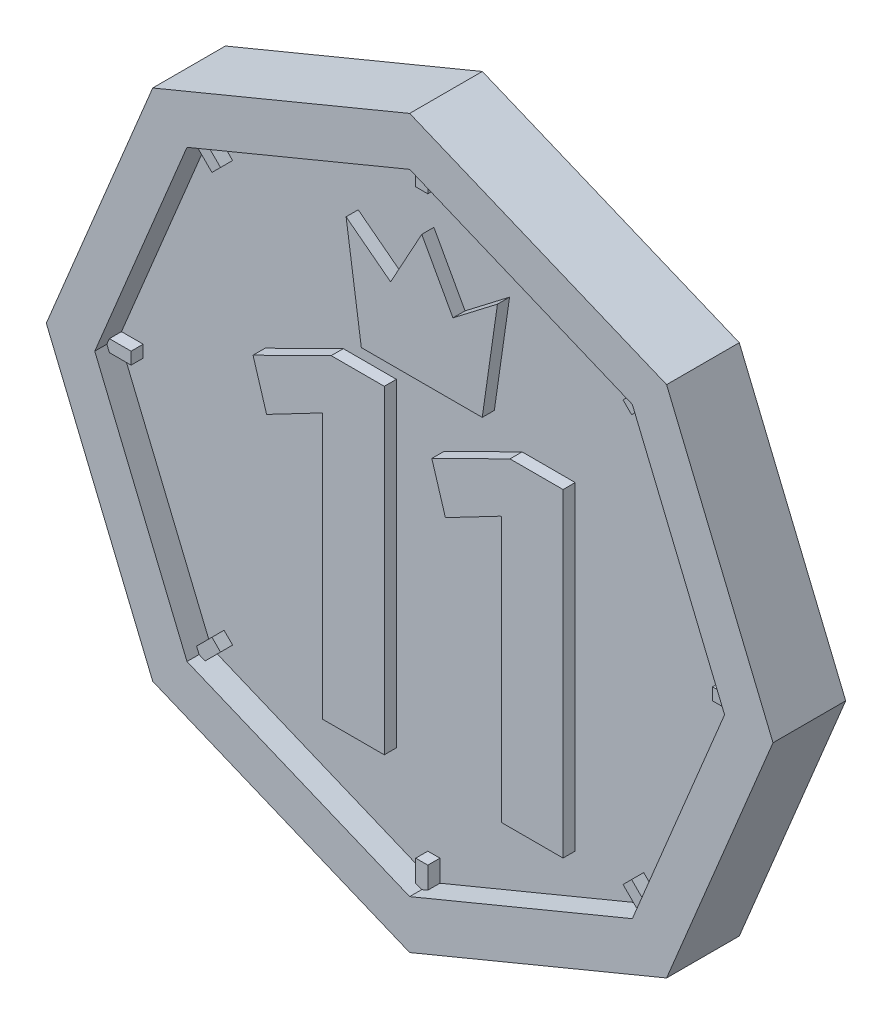
SolidWorks part; units mm, degrees
ref_plane "Front Plane" through (0, 0, 0) normal (0, 0, 1) x (1, 0, 0)
ref_plane "Top Plane" through (0, 0, 0) normal (0, 1, 0) x (1, 0, 0)
ref_plane "Right Plane" through (0, 0, 0) normal (1, 0, 0) x (0, 0, -1)
sketch "Sketch1" plane through (0, 0, 0) normal (0, 0, 1) x (1, 0, 0)
  line L0 (-26.9408, -26.9408) -> (0, -38.1)
  line L1 (38.1, 0) -> (26.9408, 26.9408)
  line L2 (26.9408, 26.9408) -> (0, 38.1)
  line L3 (0, 38.1) -> (-26.9408, 26.9408)
  line L4 (-26.9408, 26.9408) -> (-38.1, 0)
  line L5 (-38.1, 0) -> (-26.9408, -26.9408)
  line L6 (0, -38.1) -> (26.9408, -26.9408)
  line L7 (26.9408, -26.9408) -> (38.1, 0)
  line L8 (38.1, 0) -> (-38.1, 0) construction
  line L19 (33.02, 0) -> (23.3487, 23.3487)
  line L20 (23.3487, 23.3487) -> (0, 33.02)
  line L21 (0, 33.02) -> (-23.3487, 23.3487)
  line L22 (-23.3487, 23.3487) -> (-33.02, 0)
  line L23 (-33.02, 0) -> (-23.3487, -23.3487)
  line L24 (-23.3487, -23.3487) -> (0, -33.02)
  line L25 (0, -33.02) -> (23.3487, -23.3487)
  line L26 (23.3487, -23.3487) -> (33.02, 0)
  circle A0 centre (0, 0) radius 35.1998 construction
  circle A1 centre (0, 0) radius 30.5065 construction
  dimension "D1" = 76.2
  dimension "D4" = 5.08
extrude "Boss-Extrude2" add sketch "Sketch1" along normal blind 2.54 contours L25 L26 L19 L20 L21 L22 L23 L24 | L19 L20 L21 L22 L23 L24 L25 L26 region at (0, 0, 0)
extrude "Boss-Extrude3" add sketch "Sketch1<3>" along normal blind 5.08 and the other way blind 2.54 contours L6 L7 L1 L2 L3 L4 L5 L0 L26 L25 L24 L23 L22 L21 L20 L19 region at (-31.5248, -13.058, 0)
sketch "Sketch1<3>" plane through (0, 0, 0) normal (0, 0, 1) x (1, 0, 0) same geometry as "Sketch1"
sketch "Sketch2" plane through (0, 0, 2.54) normal (0, 0, 1) x (1, 0, 0)
  line L0 (-21.5859, -23.0332) -> (18.1114, -23.0332) construction
  line L2 (0, 33.02) -> (0, -33.02) construction
  line L3 (-6.3393, 13.0307) -> (6.3393, 13.0307)
  line L4 (6.3393, 13.0307) -> (7.935, 24.113)
  line L5 (7.935, 24.113) -> (3.2684, 20.5338)
  line L6 (3.2684, 20.5338) -> (0, 26.4848)
  line L7 (-3.2684, 20.5338) -> (0, 26.4848)
  line L8 (-7.935, 24.113) -> (-3.2684, 20.5338)
  line L9 (-6.3393, 13.0307) -> (-7.935, 24.113)
  line L20 (-23.7977, -22.8997) -> (-22.0016, -21.1036)
  line L21 (-0.635, -33.02) -> (0.635, -33.02)
  line L22 (-0.635, -33.02) -> (-0.635, -30.48)
  line L23 (-0.635, -30.48) -> (0.635, -30.48)
  line L24 (0.635, -33.02) -> (0.635, -30.48)
  line L25 (-0.635, -33.02) -> (0.635, -30.48) construction
  line L26 (-0.635, -30.48) -> (0.635, -33.02) construction
  line L27 (-23.7977, -22.8997) -> (-22.8997, -23.7977)
  line L28 (-22.8997, -23.7977) -> (-21.1036, -22.0016)
  line L29 (-22.0016, -21.1036) -> (-21.1036, -22.0016)
  line L30 (-33.02, 0.635) -> (-30.48, 0.635)
  line L31 (-33.02, 0.635) -> (-33.02, -0.635)
  line L32 (-33.02, -0.635) -> (-30.48, -0.635)
  line L33 (-30.48, 0.635) -> (-30.48, -0.635)
  line L34 (-22.8997, 23.7977) -> (-21.1036, 22.0016)
  line L35 (-22.8997, 23.7977) -> (-23.7977, 22.8997)
  line L36 (-23.7977, 22.8997) -> (-22.0016, 21.1036)
  line L37 (-21.1036, 22.0016) -> (-22.0016, 21.1036)
  line L38 (0.635, 33.02) -> (0.635, 30.48)
  line L39 (0.635, 33.02) -> (-0.635, 33.02)
  line L40 (-0.635, 33.02) -> (-0.635, 30.48)
  line L41 (0.635, 30.48) -> (-0.635, 30.48)
  line L42 (23.7977, 22.8997) -> (22.0016, 21.1036)
  line L43 (23.7977, 22.8997) -> (22.8997, 23.7977)
  line L44 (22.8997, 23.7977) -> (21.1036, 22.0016)
  line L45 (22.0016, 21.1036) -> (21.1036, 22.0016)
  line L46 (33.02, -0.635) -> (30.48, -0.635)
  line L47 (33.02, -0.635) -> (33.02, 0.635)
  line L48 (33.02, 0.635) -> (30.48, 0.635)
  line L49 (30.48, -0.635) -> (30.48, 0.635)
  line L50 (22.8997, -23.7977) -> (21.1036, -22.0016)
  line L51 (22.8997, -23.7977) -> (23.7977, -22.8997)
  line L52 (23.7977, -22.8997) -> (22.0016, -21.1036)
  line L53 (21.1036, -22.0016) -> (22.0016, -21.1036)
  circle A0 centre (0, 0) radius 31.75 construction
  text T0 "11" font "@Adobe Gothic Std B" height in points 110
  point P5 (0, 0)
  point P6 (0, 0)
  point P13 (0, 13.0307)
  point P15 (0, -31.75)
  point P24 (18.1114, -19.8127)
  point P26 (9.7974, -19.4567)
  point P27 (0, 0)
  point P56 (-28.0549, -19.5746)
  point P57 (-26.2491, -19.5199)
  point P58 (-22.8997, -18.9727)
  point P59 (0, 0)
  point P60 (-21.1036, -22.8997)
  point P61 (-22.8997, -22.8997)
  point P62 (-19.9988, -22.8997)
  point P63 (-21.5859, -23.0332)
  point P88 (0, 0)
  dimension "D1" = 1.27
  dimension "D2" = 2.54
  dimension "D3" = 8
extrude "Boss-Extrude4" add sketch "Sketch2" along normal blind 1.27
sketch "Sketch4" plane through (0, 0, 0) normal (0, 0, -1) x (-1, 0, 0)
  line L0 (-25.2184, -4.9787) -> (26.1518, -4.9787) construction
  line L1 (0, -7.7987) -> (0, 16.4219) construction
  line L2 (-21.4916, -19.5056) -> (21.4916, -19.5056) construction
  line L3 (-23.3147, -7.1637) -> (-23.3147, 15.7869) construction
  line L4 (23.3147, 15.7869) -> (-23.3147, 15.7869)
  line L5 (23.3147, 15.7869) -> (23.3147, 17.0569)
  line L6 (23.3147, 17.0569) -> (-23.3147, 17.0569)
  line L7 (-23.3147, 15.7869) -> (-23.3147, 17.0569)
  line L8 (23.3147, 15.7869) -> (-23.3147, 17.0569) construction
  line L9 (23.3147, 17.0569) -> (-23.3147, 15.7869) construction
  line L10 (23.3147, -8.4337) -> (-23.3147, -8.4337)
  line L11 (23.3147, -8.4337) -> (23.3147, -7.1637)
  line L12 (23.3147, -7.1637) -> (-23.3147, -7.1637)
  line L13 (-23.3147, -8.4337) -> (-23.3147, -7.1637)
  line L14 (23.3147, -8.4337) -> (-23.3147, -7.1637) construction
  line L15 (23.3147, -7.1637) -> (-23.3147, -8.4337) construction
  line L16 (0, -7.7987) -> (0, -19.5056) construction
  line L17 (-4.4689, 18.8242) -> (4.4689, 18.8242)
  line L18 (4.4689, 18.8242) -> (5.631, 27.7386)
  line L19 (5.631, 27.7386) -> (2.0605, 23.7036)
  line L20 (2.0605, 23.7036) -> (0, 27.6821)
  line L21 (-2.0605, 23.7036) -> (0, 27.6821)
  line L22 (-5.631, 27.7386) -> (-2.0605, 23.7036)
  line L23 (-4.4689, 18.8242) -> (-5.631, 27.7386)
  line L24 (0, -33.02) -> (0, -31.75) construction
  line L25 (-0.635, -33.02) -> (0.635, -33.02)
  line L26 (-0.635, -33.02) -> (-0.635, -30.48)
  line L27 (-0.635, -30.48) -> (0.635, -30.48)
  line L28 (0.635, -33.02) -> (0.635, -30.48)
  line L29 (-0.635, -33.02) -> (0.635, -30.48) construction
  line L30 (-0.635, -30.48) -> (0.635, -33.02) construction
  line L31 (-23.7977, -22.8997) -> (-22.0016, -21.1036)
  line L32 (-23.7977, -22.8997) -> (-22.8997, -23.7977)
  line L33 (-22.8997, -23.7977) -> (-21.1036, -22.0016)
  line L34 (-22.0016, -21.1036) -> (-21.1036, -22.0016)
  line L35 (-33.02, 0.635) -> (-30.48, 0.635)
  line L36 (-33.02, 0.635) -> (-33.02, -0.635)
  line L37 (-33.02, -0.635) -> (-30.48, -0.635)
  line L38 (-30.48, 0.635) -> (-30.48, -0.635)
  line L39 (-22.8997, 23.7977) -> (-21.1036, 22.0016)
  line L40 (-22.8997, 23.7977) -> (-23.7977, 22.8997)
  line L41 (-23.7977, 22.8997) -> (-22.0016, 21.1036)
  line L42 (-21.1036, 22.0016) -> (-22.0016, 21.1036)
  line L43 (0.635, 33.02) -> (0.635, 30.48)
  line L44 (0.635, 33.02) -> (-0.635, 33.02)
  line L45 (-0.635, 33.02) -> (-0.635, 30.48)
  line L46 (0.635, 30.48) -> (-0.635, 30.48)
  line L47 (23.7977, 22.8997) -> (22.0016, 21.1036)
  line L48 (23.7977, 22.8997) -> (22.8997, 23.7977)
  line L49 (22.8997, 23.7977) -> (21.1036, 22.0016)
  line L50 (22.0016, 21.1036) -> (21.1036, 22.0016)
  line L51 (33.02, -0.635) -> (30.48, -0.635)
  line L52 (33.02, -0.635) -> (33.02, 0.635)
  line L53 (33.02, 0.635) -> (30.48, 0.635)
  line L54 (30.48, -0.635) -> (30.48, 0.635)
  line L55 (22.8997, -23.7977) -> (21.1036, -22.0016)
  line L56 (22.8997, -23.7977) -> (23.7977, -22.8997)
  line L57 (23.7977, -22.8997) -> (22.0016, -21.1036)
  line L58 (21.1036, -22.0016) -> (22.0016, -21.1036)
  circle A0 centre (0, 0.6132) radius 32.3632 construction
  text T0 "TOG" font "Bree Serif" height in points 50
  text T1 "Chapter 2" font "Bree Serif" height in points 17
  point P3 (0, -7.7987)
  point P11 (0, -31.75)
  point P12 (0, 16.4219)
  point P26 (0, 18.8242)
  point P32 (21.1036, -21.1036)
  point P36 (-18.6264, -21.1036)
  point P37 (-24.5231, -18.8363)
  point P66 (0, 0)
  point P67 (-24.3263, -19.2694)
  point P68 (-20.8617, -19.7025)
  point P69 (-21.4916, -19.5056)
  dimension "D1" = 1.27
  dimension "D2" = 1.27
  dimension "D3" = 1.27
  dimension "D4" = 2.54
  dimension "D5" = 8
extrude "Boss-Extrude5" add sketch "Sketch4" along normal blind 1.27
